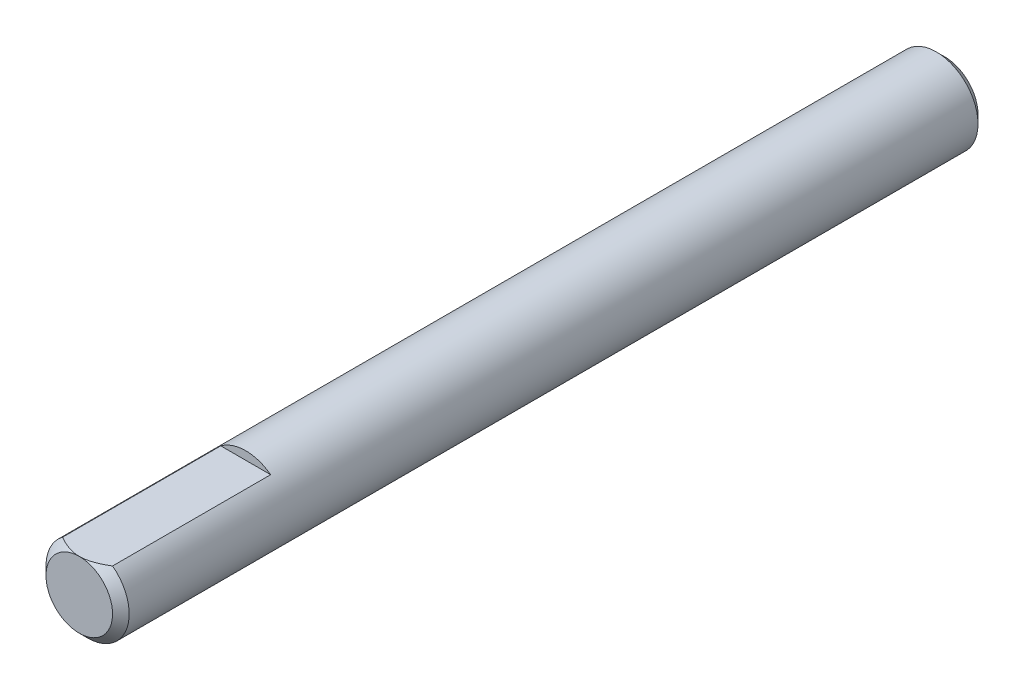
SolidWorks part; units mm, degrees
ref_plane "Front Plane" through (0, 0, 0) normal (0, 0, 1) x (1, 0, 0)
ref_plane "Top Plane" through (0, 0, 0) normal (0, 1, 0) x (1, 0, 0)
ref_plane "Right Plane" through (0, 0, 0) normal (1, 0, 0) x (0, 0, -1)
sketch "Sketch1" plane through (0, 0, 0) normal (0, 0, 1) x (1, 0, 0)
  circle A0 centre (0, 0) radius 2.5
  dimension "D1" = 5
extrude "Boss-Extrude1" add sketch "Sketch1" along normal blind 52
sketch "Sketch2" plane through (0, 0, 52) normal (0, 0, 1) x (1, 0, 0)
  line L1 (-3.7629, 4.3396) -> (3.7053, 4.3396)
  line L2 (-3.7629, 4.3396) -> (-3.7629, 2)
  line L3 (-3.7629, 2) -> (3.7053, 2)
  line L4 (3.7053, 4.3396) -> (3.7053, 2)
  dimension "D1" = 2
extrude "Cut-Extrude1" cut sketch "Sketch2" against normal blind 10
chamfer "Chamfer1" distance 0.5 angle 45 2 edges at (2.5, 0, 0) (0, -2.5, 52)
